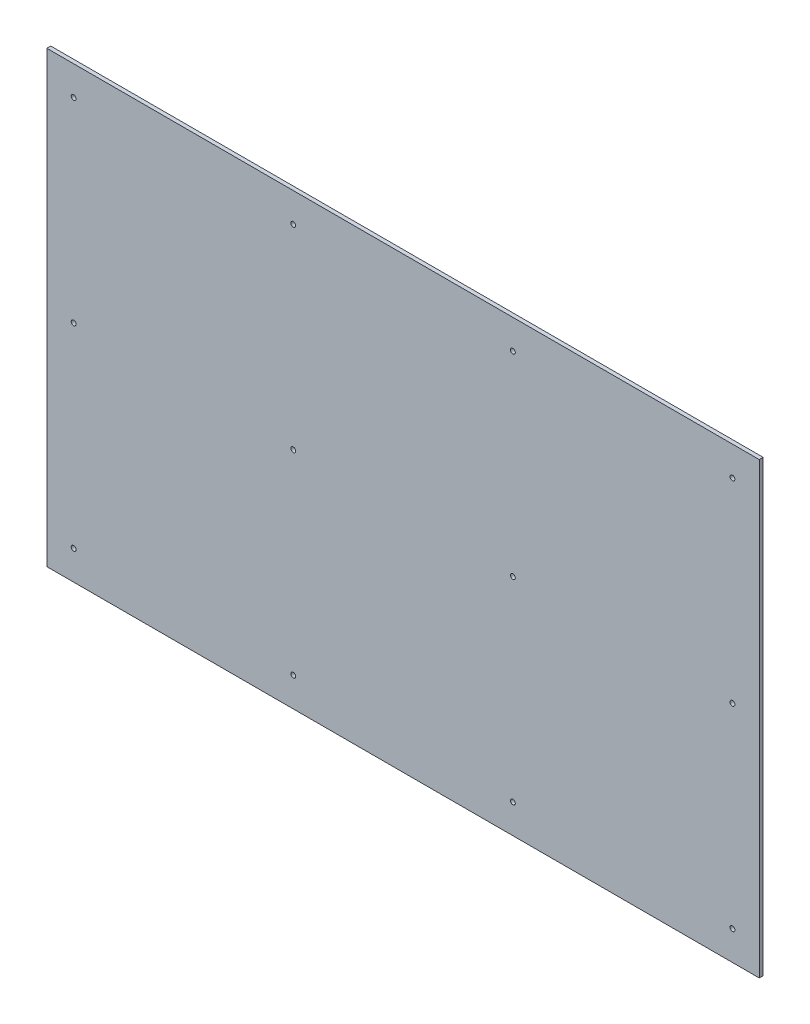
SolidWorks part; units mm, degrees
ref_plane "Ön Düzlem" through (0, 0, 0) normal (0, 0, 1) x (1, 0, 0)
ref_plane "Üst Düzlem" through (0, 0, 0) normal (0, 1, 0) x (1, 0, 0)
ref_plane "Sağ Düzlem" through (0, 0, 0) normal (1, 0, 0) x (0, 0, -1)
sketch "Çizim1" plane through (0, 0, 0) normal (0, 0, 1) x (1, 0, 0)
  line L0 (2381.6011, 1497.7378) -> (3841.6011, 1497.7378)
  line L1 (3841.6011, 1497.7378) -> (3841.6011, 2417.7378)
  line L2 (3841.6011, 2417.7378) -> (2381.6011, 2417.7378)
  line L3 (2381.6011, 2417.7378) -> (2381.6011, 1497.7378)
  circle A0 centre (2436.6011, 2357.7378) radius 5
  circle A1 centre (2886.6011, 2357.7378) radius 5
  circle A2 centre (3336.6011, 2357.7378) radius 5
  circle A3 centre (3786.6011, 2357.7378) radius 5
  circle A4 centre (2436.6011, 1957.7378) radius 5
  circle A5 centre (2886.6011, 1957.7378) radius 5
  circle A6 centre (3336.6011, 1957.7378) radius 5
  circle A7 centre (3786.6011, 1957.7378) radius 5
  circle A8 centre (2436.6011, 1557.7378) radius 5
  circle A9 centre (2886.6011, 1557.7378) radius 5
  circle A10 centre (3336.6011, 1557.7378) radius 5
  circle A11 centre (3786.6011, 1557.7378) radius 5
  dimension "D12" = 10
  dimension "D1" = 1460
  dimension "D2" = 920
  dimension "D3" = 55
  dimension "D4" = 450
  dimension "D5" = 450
  dimension "D6" = 450
  dimension "D7" = 55
  dimension "D8" = 60
  dimension "D9" = 400
  dimension "D10" = 400
  dimension "D11" = 60
base flange "Taban-Flanş1" sketch "Çizim1" thickness 8 reverse thickness direction no parameters "D1"=4
sketch "Büküm-Çizgileri1" [suppressed] plane through (0, 0, 0) normal (0, 1, 0) x (1, 0, 0)
sketch "Sınırlandırma-Kutusu1" [suppressed] plane through (0, 0, 0) normal (0, 1, 0) x (1, 0, 0)
sheet metal parameters "Sac-Levha1" thickness 8 parameters "D1"=4
flat pattern "Düz-Çoğaltma1" [suppressed]
sketch "Büküm-Çizgileri2" plane through (0, 0, 0) normal (0, 1, 0) x (1, 0, 0)
sketch3d "Sınırlandırma-Kutusu2" [suppressed]
  line L0 (2381.6011, 1497.7378, 0) -> (3841.6011, 1497.7378, 0) construction
  line L1 (2381.6011, 2417.7378, 0) -> (3841.6011, 2417.7378, 0) construction
  line L2 (2381.6011, 1497.7378, 0) -> (2381.6011, 2417.7378, 0) construction
  line L3 (3841.6011, 1497.7378, 0) -> (3841.6011, 2417.7378, 0) construction
